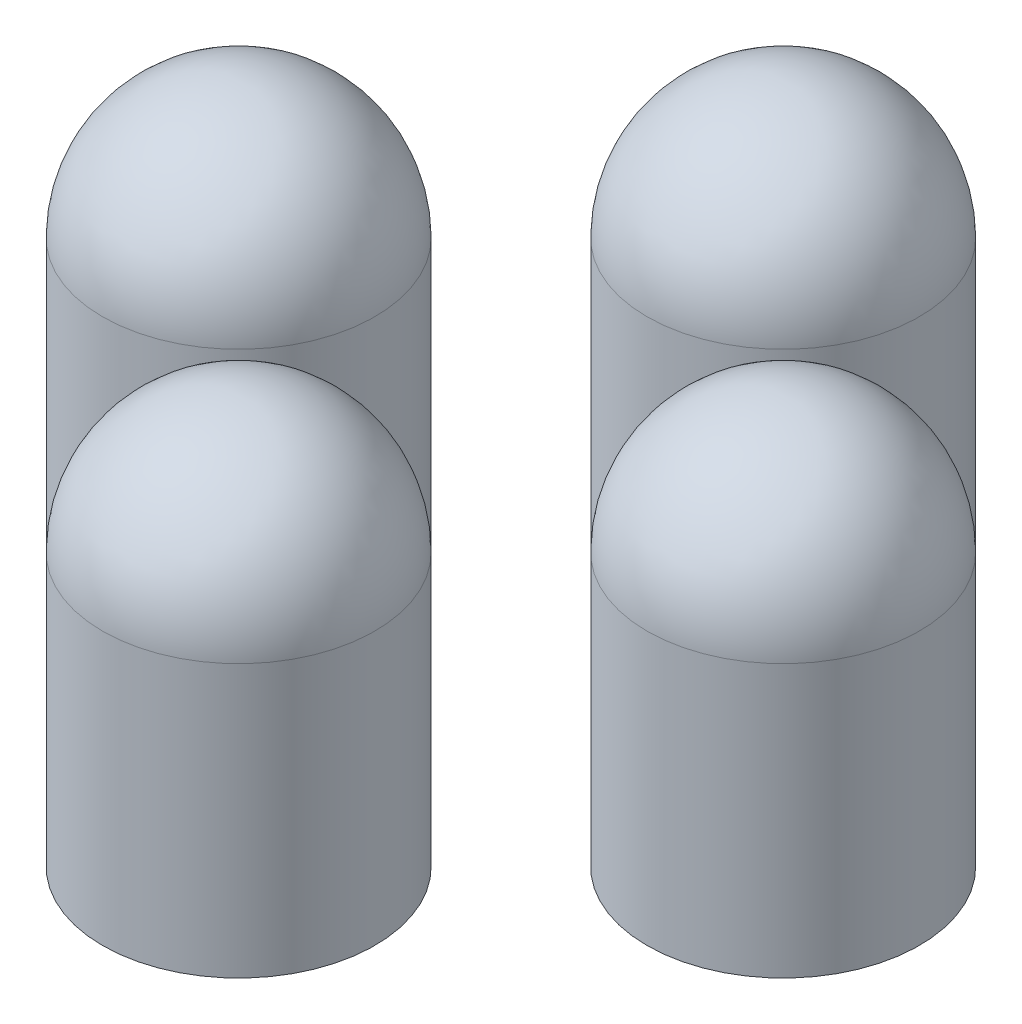
SolidWorks part; units mm, degrees
ref_plane "Front Plane" through (0, 0, 0) normal (0, 0, 1) x (1, 0, 0)
ref_plane "Top Plane" through (0, 0, 0) normal (0, 1, 0) x (1, 0, 0)
ref_plane "Right Plane" through (0, 0, 0) normal (1, 0, 0) x (0, 0, -1)
sketch "Sketch1" plane through (0, 0, 0) normal (0, 1, 0) x (1, 0, 0)
  circle A0 centre (0, 0) radius 5
  circle A1 centre (10, 10) radius 5
  circle A2 centre (20, 0) radius 5
  circle A3 centre (10, -10) radius 5
  point P12 (10, 0)
  dimension "D1" = 4
extrude "Boss-Extrude1" add sketch "Sketch1" along normal blind 10
dome "Dome4" faces to dome 1 distance 5 reverse direction no elliptical dome no face at (0, 10, 5) parameters "D1"=5
dome "Dome5" faces to dome 1 distance 5 reverse direction no elliptical dome no face at (10, 10, -5) parameters "D1"=5
dome "Dome6" faces to dome 1 distance 5 reverse direction no elliptical dome no face at (20, 10, 5) parameters "D1"=5
dome "Dome7" faces to dome 1 distance 5 reverse direction no elliptical dome no face at (10, 10, 15) parameters "D1"=5
